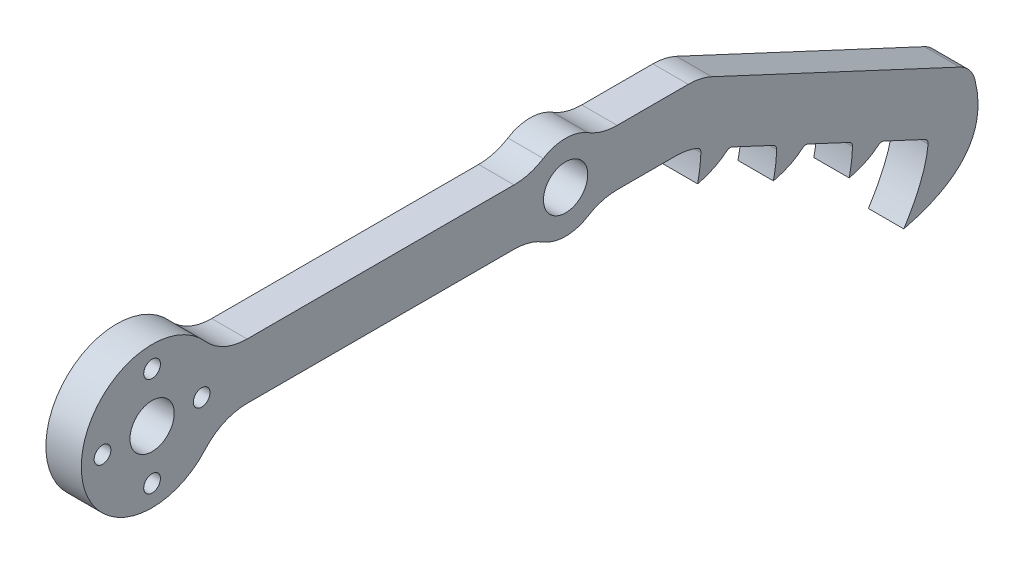
SolidWorks part; units mm, degrees
material "6061 Alloy"
ref_plane "Front Plane" through (0, 0, 0) normal (0, 0, 1) x (1, 0, 0)
ref_plane "Top Plane" through (0, 0, 0) normal (0, 1, 0) x (1, 0, 0)
ref_plane "Right Plane" through (0, 0, 0) normal (1, 0, 0) x (0, 0, -1)
sketch "Sketch1" plane through (0, 0, 0) normal (1, 0, 0) x (0, 0, -1)
  line L0 (-57.9219, 44.5435) -> (-40.0493, 54.8622)
  line L1 (-40.0493, 49.8622) -> (56.1047, 49.8622)
  line L2 (56.1047, 49.8622) -> (102.5472, 28.2057)
  line L3 (-40.0493, 59.8622) -> (58.3217, 59.8622)
  line L4 (58.3217, 59.8622) -> (106.7734, 37.2688)
  line L5 (56.1047, 49.8622) -> (84.5622, 36.5923) construction
  line L6 (58.3217, 59.8622) -> (88.7883, 45.6554) construction
  line L7 (102.5472, 28.2057) -> (106.7734, 37.2688)
  line L8 (102.5472, 28.2057) -> (111.6103, 23.9795)
  line L9 (93.4842, 32.4319) -> (106.7734, 37.2688)
  line L10 (56.1047, 49.8622) -> (58.3217, 59.8622) construction
  circle A0 centre (-57.9219, 44.5435) radius 15.875
  circle A1 centre (-40.0493, 54.8622) radius 4.7625
  circle A2 centre (-40.0493, 54.8622) radius 2.5
  circle A3 centre (-40.0493, 54.8622) radius 5
  circle A4 centre (-40.0493, 54.8622) radius 12.7
  circle A6 centre (34.1047, 54.8622) radius 7.62
  parabola Q0 (106.7734, 37.2688) -> (94.7552, 18.0752) focus (102.5472, 28.2057) apex (107.0788, 26.0926)
  parabola Q1 (99.1632, 29.7837) -> (94.7552, 18.0752) focus (93.4842, 32.4319) apex (98.5101, 34.2612)
  parabola Q2 (93.4202, 43.4955) -> (84.9631, 30.8885) focus (87.9414, 37.2725) apex (91.341, 34.5621)
  parabola Q3 (85.5686, 36.123) -> (84.9631, 30.8885) focus (78.3442, 40.2408) apex (83.762, 43.3694)
  parabola Q4 (79.8256, 49.8348) -> (71.3685, 37.2277) focus (74.3468, 43.6117) apex (77.7464, 40.9013)
  parabola Q5 (71.974, 42.4623) -> (71.3685, 37.2277) focus (64.7496, 46.58) apex (70.1674, 49.7086)
  parabola Q6 (66.2309, 56.1741) -> (57.7739, 43.567) focus (60.7522, 49.951) apex (64.1518, 47.2406)
  parabola Q7 (58.3794, 48.8015) -> (57.7739, 43.567) focus (51.155, 52.9193) apex (56.5728, 56.0479)
  point P12 (93.4842, 32.4319)
  point P19 (100.1288, 34.8504)
  point P46 (57.2132, 54.8622)
  point P47 (34.1047, 54.8622)
  dimension "D1" = 10
  dimension "D5" = 10
  dimension "D2" = 12.4745
  dimension "D3" = 5
  dimension "D4" = 15
  dimension "D6" = 5
  dimension "D7" = 22
extrude "Boss-Extrude1" add sketch "Sketch1" along normal blind 6.35 contours A0 A4 L0 A3 | L0 A4 A0 A3 | A0 A4 L1 A3 | L3 A4 A0 A3 | L0 A3 A0 | A0 A3 L0 | A3 A0 A1 | A2 A1 | A2 | L1 A4 L3 A3 | A6 L3 A4 L1 | L3 A6 L1 | L3 A6 | L1 A6 | Q6 L4 L3 A6 L1 L2 | L2 Q7 Q6 | L4 Q6 L2 Q4 | L2 Q5 Q4 | L4 Q4 L2 Q2 | L2 Q3 Q2 | L4 Q2 L2 L9 | L9 L2 L7 | Q0 L7 L8 | L2 Q1 Q0 L8 | A6 region at (0, 53.7938, 49.4225) region at (0, 47.279, 45.6612) region at (0, 52.862, 44.5166) region at (0, 51.9936, 44.0152) region at (0, 62.2646, 41.1006) region at (0, 46.6449, 36.6917) region at (0, 57.2087, 40.6781) region at (0, 53.0598, 44.5079) region at (0, 59.3323, 41.2471) region at (0, 54.8622, 31.9722) region at (0, 54.8622, 0.304) region at (0, 60.9274, -34.1047) region at (0, 54.8622, -34.1047) region at (0, 48.7971, -34.1047) region at (0, 54.2453, -53.6216) region at (0, 47.8087, -72.3396) region at (0, 46.1053, -60.0268) region at (0, 41.4694, -85.9342) region at (0, 37.45, -97.3772) region at (0, 39.7661, -73.6214) region at (0, 30.7591, -105.9447) region at (0, 32.6355, -100.9349) region at (0, 33.4268, -87.216) region at (0, 23.9786, -100.9688)
sketch "Sketch7" plane through (6.35, 0, 0) normal (1, 0, 0) x (0, 0, -1)
  point P0 (-40.0493, 54.8622)
  point P1 (34.1047, 54.8622)
hole_wizard "5/16 (0.3125) Dowel Hole1" positions "Sketch7" profile "Sketch8" hole size "5/16" standard "ANSI Inch" end condition through all
sketch "Sketch8" plane through (6.35, 54.8622, 40.0493) normal (0, 1, 0) x (0, 0, -1)
  line L0 (0, 0) -> (0, 6.35)
  line L1 (0, 6.35) -> (3.9687, 6.35)
  line L2 (3.9687, 6.35) -> (3.9687, 0)
  line L5 (3.9687, 0) -> (0, 0)
  line L11 (0, -6.35) -> (0, 107.95) construction
  dimension "Thru Hole Dia." = 7.9375
  dimension "Thru Hole Depth" = 6.35
fillet "Fillet1" radius 10 2 edges at (3.175, 59.8622, 28.375) (3.175, 49.8622, 28.375)
fillet "Fillet2" radius 10 2 edges at (3.175, 49.8622, -56.1047) (3.175, 59.8622, -58.3217)
fillet "Fillet4" radius 5 1 edges at (3.175, 37.2688, -106.7734)
fillet "Fillet5" radius 1 7 edges at (3.175, 33.7664, -90.6224) (3.175, 40.1057, -77.0278) (3.175, 46.4449, -63.4331) (3.175, 48.8015, -58.3794) (3.175, 42.4623, -71.974) (3.175, 36.123, -85.5686) (3.175, 29.7837, -99.1632)
fillet "Fillet6" radius 10 4 edges at (3.175, 49.8622, -28.3545) (3.175, 49.8622, -39.8549) (3.175, 59.8622, -28.3545) (3.175, 59.8622, -39.8549)
sketch "Sketch9" plane through (6.35, 0, 0) normal (1, 0, 0) x (0, 0, -1)
  point P0 (-40.0493, 54.8622)
  point P1 (-40.0493, 62.7997)
  point P6 (-33.1752, 50.8935)
  point P7 (-46.9234, 50.8935)
  point P8 (-40.0493, 54.8622)
  dimension "D1" = 7.9375
  dimension "D2" = 3
sketch "Sketch10" plane through (6.35, 0, 0) normal (1, 0, 0) x (0, 0, -1)
  point P0 (-40.0493, 63.7522)
  point P1 (-40.0493, 54.8622)
  point P5 (-40.0493, 54.8622)
  dimension "D1" = 8.89
hole_wizard "Ø3.0mm Dowel Hole1" positions "Sketch10" profile "Sketch11" hole size "Ø3.0" standard "ANSI Metric" end condition through all
sketch "Sketch11" plane through (6.35, 63.7522, 40.0493) normal (0, 1, 0) x (0, 0, -1)
  line L0 (0, 0) -> (0, 6.35)
  line L1 (0, 6.35) -> (1.5, 6.35)
  line L2 (1.5, 6.35) -> (1.5, 0)
  line L5 (1.5, 0) -> (0, 0)
  line L11 (0, -6.35) -> (0, 107.95) construction
  dimension "Thru Hole Dia." = 3
  dimension "Thru Hole Depth" = 6.35
pattern_circular "CirPattern1" count 4 over 360 about axis through (6.35, 54.8622, 40.0493) along (1, 0, 0) of "Ø3.0mm Dowel Hole1"
